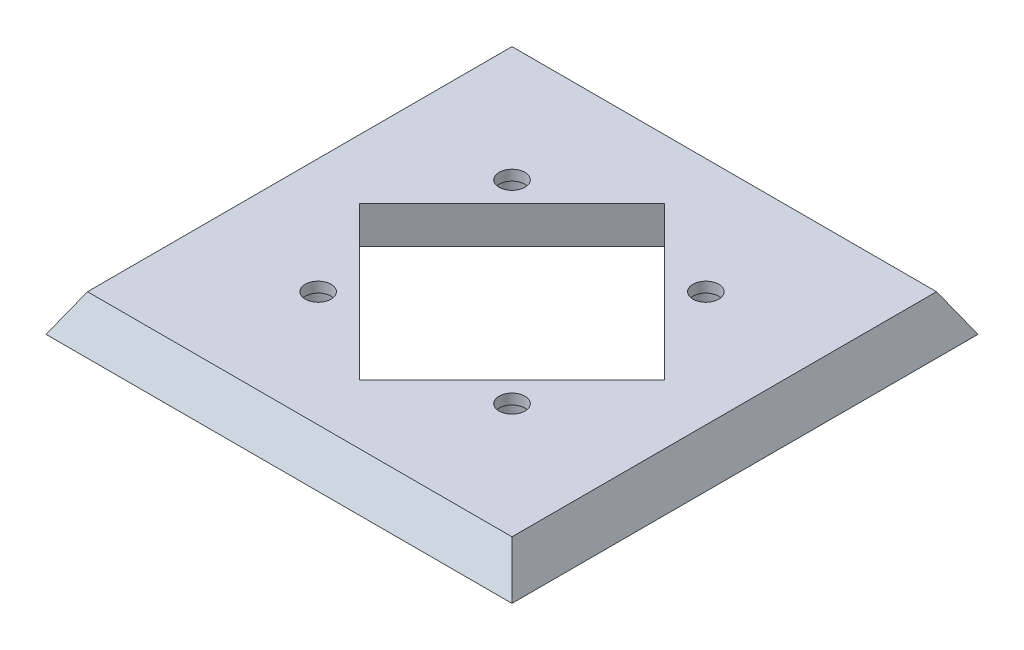
SolidWorks part; units mm, degrees
material "Stainless Steel (ferritic)"
ref_plane "Front Plane" through (0, 0, 0) normal (0, 0, 1) x (1, 0, 0)
ref_plane "Top Plane" through (0, 0, 0) normal (0, 1, 0) x (1, 0, 0)
ref_plane "Right Plane" through (0, 0, 0) normal (1, 0, 0) x (0, 0, -1)
sketch "Sketch2" plane through (0, 0, 0) normal (0, 1, 0) x (1, 0, 0)
  line L0 (-39.3576, 0) -> (0, 39.3576)
  line L1 (-39.3576, 0) -> (0, -39.3576)
  line L2 (0, 39.3576) -> (39.3576, 0)
  line L3 (0, -39.3576) -> (39.3576, 0)
  line L4 (-39.3576, 0) -> (39.3576, 0) construction
  line L5 (0, 39.3576) -> (0, -39.3576) construction
  circle A0 centre (-25, 25) radius 3.34
  circle A1 centre (25, 25) radius 3.34
  circle A2 centre (25, -25) radius 3.34
  circle A3 centre (-25, -25) radius 3.34
  point P0 (0, 0)
  point P2 (0, 0)
  point P14 (0, 0)
  dimension "D2" = 6.68
  dimension "D1" = 55.66
  dimension "D3" = 50
ref_plane "Plane1" through (0, 9.525, 0) normal (0, 1, 0) x (1, 0, 0)
sketch "Sketch5" plane through (0, 0, 0) normal (1, 0, 0) x (0, 0, -1)
  line L0 (60.1, 0) -> (-60.1, 0)
  line L1 (-39.3576, 0) -> (0, 0) construction
  line L2 (-60.1, 0) -> (-54.75, 9.525)
  line L3 (-54.75, 9.525) -> (54.75, 9.525)
  line L4 (54.75, 9.525) -> (60.1, 0)
  line L5 (0, 0) -> (39.3576, 0) construction
  point P0 (0, 9.525)
  dimension "D1" = 0
  dimension "D2" = 120.2
  dimension "D3" = 109.5
  dimension "D4" = 9.525
extrude "Boss-Extrude1" add sketch "Sketch5" along normal blind 60.1 and the other way blind 60.1
sketch "Sketch6" plane through (0, 0, 0) normal (0, 0, 1) x (1, 0, 0)
  line L0 (0, 0) -> (0, 9.525) construction
  line L2 (-60.1, 9.525) -> (60.1, 9.525) construction
  line L3 (0, 9.525) -> (-54.75, 9.525) construction
  line L4 (-54.75, 9.525) -> (-60.1, 0)
  line L5 (-60.1, 0) -> (-60.1, 9.525)
  line L6 (-60.1, 9.525) -> (-54.75, 9.525)
  line L7 (60.1, 9.525) -> (54.75, 9.525)
  line L8 (60.1, 0) -> (60.1, 9.525)
  line L9 (54.75, 9.525) -> (60.1, 0)
  dimension "D1" = 54.75
extrude "Cut-Extrude3" cut sketch "Sketch6" against normal through all both and the other way through all
extrude "Cut-Extrude5" cut sketch "Sketch2" along normal through all
sketch "Sketch7" plane through (0, 9.525, 0) normal (0, 1, 0) x (1, 0, 0)
  line L0 (0, 54.75) -> (0, -54.75) construction
  line L1 (-54.75, 54.75) -> (54.75, 54.75) construction
  line L2 (-54.75, -54.75) -> (54.75, -54.75) construction
  line L4 (-54.75, 54.75) -> (-54.75, -54.75) construction
  line L5 (-54.75, 0) -> (54.75, 0) construction
  line L6 (54.75, 54.75) -> (54.75, -54.75) construction
  point P6 (0, 0)
sketch "Sketch8" plane through (0, 0, 0) normal (0, -1, 0) x (1, 0, 0)
  circle A0 centre (-25, 25) radius 5.08
  circle A1 centre (25, 25) radius 5.08
  circle A2 centre (25, -25) radius 5.08
  circle A3 centre (-25, -25) radius 5.08
  point P12 (0, 0)
  dimension "D1" = 10.16
extrude "Cut-Extrude6" cut sketch "Sketch8" against normal blind 6.858
